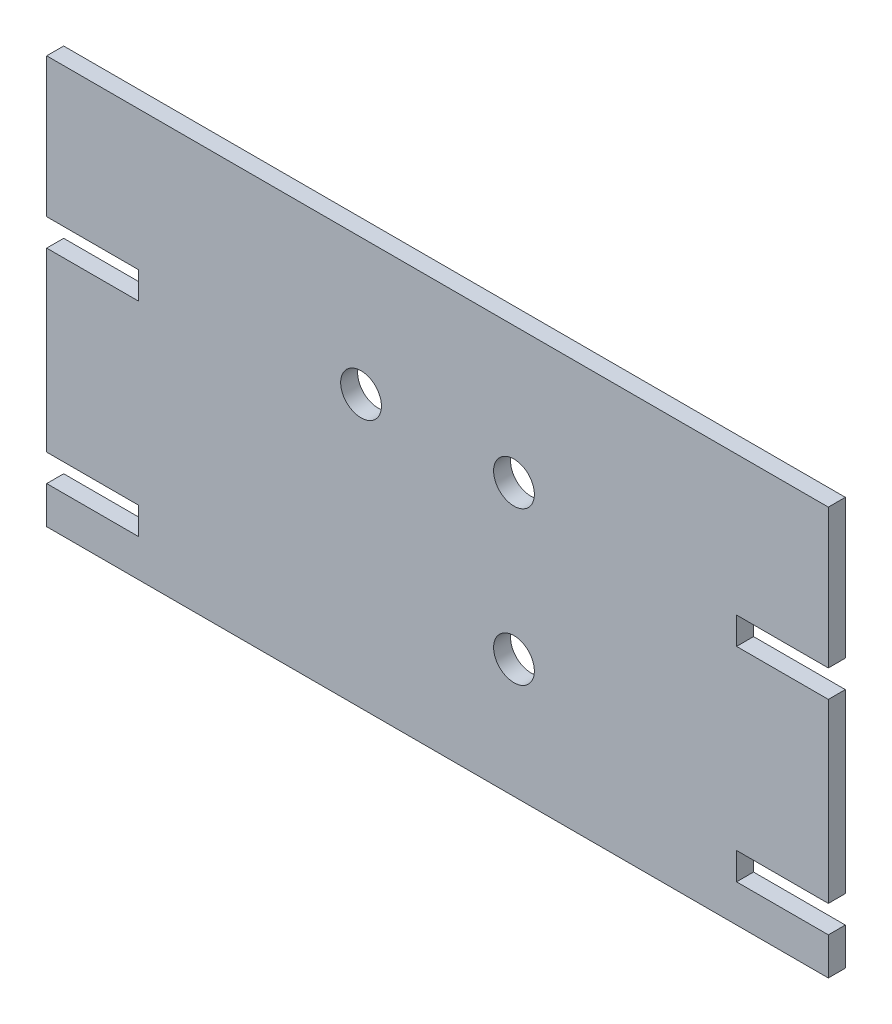
SolidWorks part; units mm, degrees
ref_plane "Front Plane" through (0, 0, 0) normal (0, 0, 1) x (1, 0, 0)
ref_plane "Top Plane" through (0, 0, 0) normal (0, 1, 0) x (1, 0, 0)
ref_plane "Right Plane" through (0, 0, 0) normal (1, 0, 0) x (0, 0, -1)
sketch "Sketch1" plane through (0, 0, 0) normal (0, 0, 1) x (1, 0, 0)
  line L1 (-115, -60) -> (115, -60)
  line L2 (-115, -60) -> (-115, 60)
  line L3 (-115, 60) -> (115, 60)
  line L4 (115, -60) -> (115, 60)
  line L5 (-115, -60) -> (115, 60) construction
  line L6 (-115, 60) -> (115, -60) construction
  point P0 (0, 0)
  dimension "D1" = 230
  dimension "D2" = 120
extrude "Boss-Extrude1" add sketch "Sketch1" along normal blind 5
sketch "Sketch2" plane through (0, 0, 0) normal (0, 0, -1) x (-1, 0, 0)
  line L0 (115, 11) -> (88, 11)
  line L1 (115, 60) -> (115, -60) construction
  line L2 (88, 11) -> (88, 19)
  line L3 (88, 19) -> (115, 19)
  line L4 (115, 19) -> (115, 11)
  line L5 (117.8, 19) -> (115.5, 19) construction
  line L6 (115.5, 11) -> (117.8, 11) construction
  line L7 (115, -49) -> (88, -49)
  line L8 (88, -41) -> (115, -41)
  line L9 (88, -49) -> (88, -41)
  line L10 (115, -41) -> (115, -49)
  line L11 (115.5, -49) -> (117.8, -49) construction
  line L12 (117.8, -41) -> (115.5, -41) construction
  line L13 (115, -40.5) -> (115, -30.5) construction
  line L14 (0, 2.75) -> (0, -2.75) construction
  line L15 (-115, -41) -> (-115, -49)
  line L16 (-88, -49) -> (-88, -41)
  line L17 (-88, -41) -> (-115, -41)
  line L18 (-115, -49) -> (-88, -49)
  line L19 (-115, 19) -> (-115, 11)
  line L20 (-88, 19) -> (-115, 19)
  line L21 (-88, 11) -> (-88, 19)
  line L22 (-115, 11) -> (-88, 11)
  dimension "D1" = 27
  dimension "D2" = 27
extrude "Cut-Extrude1" cut sketch "Sketch2" against normal up to next
sketch "Sketch3" plane through (0, 0, 5) normal (0, 0, 1) x (1, 0, 0)
  line L0 (-115, 20) -> (115, 20) construction
  line L1 (-115, 60) -> (-115, 19) construction
  line L2 (115, 19) -> (115, 60) construction
  line L3 (115, 60) -> (-115, 60) construction
  line L4 (22.5, 60) -> (22.5, -60) construction
  line L5 (-115, -60) -> (115, -60) construction
  circle A0 centre (22.5, 20) radius 6
  circle A1 centre (-22.5, 20) radius 6
  circle A2 centre (22.5, -25) radius 6
  dimension "D2" = 12
  dimension "D3" = 45
  dimension "D1" = 40
  dimension "D4" = 45
  dimension "D5" = 22.5
extrude "Cut-Extrude2" cut sketch "Sketch3" against normal up to next
